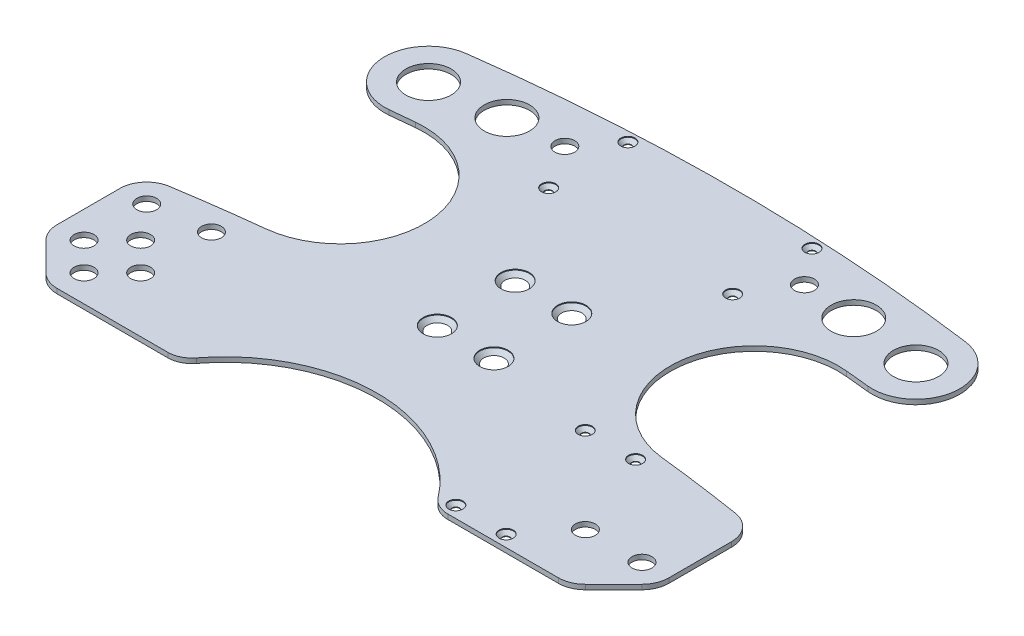
SolidWorks part; units mm, degrees
ref_plane "Front Plane" through (0, 0, 0) normal (0, 0, 1) x (1, 0, 0)
ref_plane "Top Plane" through (0, 0, 0) normal (0, 1, 0) x (1, 0, 0)
ref_plane "Right Plane" through (0, 0, 0) normal (1, 0, 0) x (0, 0, -1)
sketch "Sketch1" plane through (0, 0, 0) normal (0, 1, 0) x (1, 0, 0)
  line L1 (-120, -95) -> (120, -95)
  line L2 (-120, -95) -> (-120, 95)
  line L3 (-120, 95) -> (120, 95)
  line L4 (120, -95) -> (120, 95)
  line L5 (-120, -95) -> (120, 95) construction
  line L6 (-120, 95) -> (120, -95) construction
  line L7 (-10, 13.75) -> (10, 13.75)
  line L8 (-10, 13.75) -> (-10, -13.75)
  line L9 (-10, -13.75) -> (10, -13.75)
  line L10 (10, 13.75) -> (10, -13.75)
  line L11 (-10, 13.75) -> (10, -13.75) construction
  line L12 (-10, -13.75) -> (10, 13.75) construction
  circle A0 centre (0, 0) radius 95
  circle A1 centre (-10, 13.75) radius 2.5
  circle A2 centre (10, 13.75) radius 2.5
  circle A3 centre (10, -13.75) radius 2.5
  circle A4 centre (-10, -13.75) radius 2.5
  circle A5 centre (0, 0) radius 120
  dimension "D3" = 5
  dimension "D1" = 240
  dimension "D2" = 190
  dimension "D4" = 27.5
  dimension "D5" = 20
extrude "Boss-Extrude1" add sketch "Sketch1" along normal blind 1.7 contours A0 A4 L8 A1 L7 A2 L10 A3 L9 | A4 L9 A3 L10 A2 L7 A1 L8 | L3 A5 L1 A0 | L1 A5 L3 A0 region at (-105.6812, 0, 51.9346) region at (68.7642, 0, 68.7642) region at (-92.313, 0, 0) region at (0, 0, 0)
sketch "Sketch2" plane through (0, 1.7, 0) normal (0, 1, 0) x (1, 0, 0)
  line L0 (-81.1673, -40) -> (21.9115, -40) construction
  line L1 (-127.3056, -60) -> (138.909, -60) construction
  line L2 (-88.5406, 28.139) -> (-88.5406, -89.0376) construction
  line L3 (-88.5406, -40) -> (-88.5406, -60) construction
  line L4 (0, 21.6044) -> (0, -21.4213) construction
  line L5 (88.5406, 33.139) -> (88.5406, -84.0376) construction
  line L6 (-151.9803, -25) -> (55.006, -25) construction
  line L7 (-48.8837, 35) -> (62.426, 35) construction
  circle A0 centre (0, 0) radius 35
  circle A1 centre (0, 35) radius 2.5
  circle A2 centre (30.3109, 17.5) radius 2.5
  circle A3 centre (30.3109, -17.5) radius 2.5
  circle A4 centre (0, -35) radius 2.5
  circle A5 centre (-30.3109, -17.5) radius 2.5
  circle A6 centre (-30.3109, 17.5) radius 2.5
  circle A7 centre (-88.5406, -40) radius 3.5
  circle A8 centre (-88.5406, -50) radius 10
  circle A9 centre (-78.5406, -50) radius 3.5
  circle A10 centre (-88.5406, -60) radius 3.5
  circle A11 centre (-98.5406, -50) radius 3.5
  circle A12 centre (78.5406, -50) radius 3.5
  circle A13 centre (98.5406, -50) radius 3.5
  circle A14 centre (-98.5406, -27.8625) radius 3.5
  circle A15 centre (-78.5406, -25) radius 3.5
  circle A16 centre (0, 0) radius 45
  circle A17 centre (0, -580) radius 625
  circle A18 centre (0, -580) radius 645
  circle A19 centre (-86.0945, 59.2282) radius 8
  circle A20 centre (-61.2596, 62.0843) radius 8
  circle A21 centre (-86.0945, 59.2282) radius 15.5
  arc A22 (-73.3144, 95) -> (-73.3144, -95) centre (0, 0) ccw construction
  circle A23 centre (-61.2596, 62.0843) radius 9.5
  circle A24 centre (-86.0945, 59.2282) radius 9.5
  circle A25 centre (61.2596, 62.0843) radius 8
  circle A26 centre (86.0945, 59.2282) radius 8
  circle A27 centre (-42.3209, 63.6101) radius 3.5
  circle A28 centre (0, 0) radius 70
  circle A29 centre (42.3209, 63.6101) radius 3.5
  circle A30 centre (-98.5406, -50) radius 9.5
  circle A31 centre (42.3209, 63.6101) radius 9.5
  circle A32 centre (61.2596, 62.0843) radius 9.5
  circle A33 centre (0, -645.0455) radius 625
  point P17 (0, 0)
  point P21 (-88.5406, -50)
  point P37 (-88.5406, -50)
  point P56 (0, 65)
  point P57 (0, 45)
  point P68 (-76.6704, 60.4269)
  point P69 (-70.7097, 61.1124)
  point P81 (0, 0)
  dimension "D1" = 70
  dimension "D2" = 5
  dimension "D4" = 7
  dimension "D9" = 90
  dimension "D10" = 1250
  dimension "D11" = 20
  dimension "D12" = 16
  dimension "D14" = 6
  dimension "D13" = 19
  dimension "D17" = 140
  dimension "D18" = 6
  dimension "D5" = 20
  dimension "D6" = 40
  dimension "D8" = 15
  dimension "D15" = 6
  dimension "D3" = 6
  dimension "D7" = 4
extrude "Cut-Extrude1" cut sketch "Sketch2" against normal up to next contours A7 | A9 | A10 | A11 | A12 | A13 | A14 | A15 | A19 | A20 | A25 | A26 | A27 | A29
sketch "Sketch3" plane through (0, 1.7, 0) normal (0, 1, 0) x (1, 0, 0)
  line L1 (-84.5506, 43.8053) -> (-40.7771, 48.1872)
  line L2 (0, 100.6986) -> (0, -98.8678) construction
  line L3 (-10.3445, 0) -> (20.4144, 0) construction
  line L5 (84.5506, 43.8053) -> (40.7771, 48.1872)
  line L6 (-42.3209, 63.6101) -> (0, 0) construction
  line L7 (-36.306, 26.5871) -> (-55.2257, 55.0243)
  line L8 (-10.4964, 43.7587) -> (-29.4161, 72.1959)
  line L9 (10.4964, 43.7587) -> (29.4161, 72.1959)
  line L10 (36.306, 26.5871) -> (55.2257, 55.0243)
  line L11 (-108.0406, -50) -> (-108.0406, -27.8625)
  line L13 (-73.3144, -95) -> (73.3144, -95)
  line L14 (73.3144, 95) -> (-73.3144, 95)
  line L15 (-73.3144, -95) -> (73.3144, -95)
  line L16 (73.3144, 95) -> (-73.3144, 95)
  line L17 (-69.0406, -25) -> (-69.0406, -50)
  line L18 (-71.8231, -56.7175) -> (-81.8231, -66.7175)
  line L19 (-105.2581, -56.7175) -> (-95.2581, -66.7175)
  line L20 (-42.3209, 79.1101) -> (42.3209, 79.1101)
  line L21 (-78.5406, -15.5) -> (-42.2463, -15.5)
  line L22 (0, -45) -> (111.243, -45) construction
  line L23 (-88.5406, -69.5) -> (88.5406, -69.5)
  line L24 (69.0406, -15.5) -> (45.0406, -15.5)
  line L25 (78.5406, -15.5) -> (42.2463, -15.5)
  line L27 (108.0406, -50) -> (108.0406, -27.8625)
  line L28 (105.2581, -56.7175) -> (95.2581, -66.7175)
  line L29 (69.0406, -15.5) -> (69.0406, -69.5)
  line L30 (69.0406, -69.5) -> (45.0406, -69.5)
  line L31 (45.0406, -15.5) -> (45.0406, -69.5)
  line L32 (57.0406, -15.5) -> (57.0406, -69.5) construction
  line L33 (45.0406, -42.5) -> (69.0406, -42.5) construction
  circle A0 centre (-86.0945, 59.2282) radius 15.5
  arc A1 (-73.3144, 95) -> (-73.3144, -95) centre (0, 0) ccw construction
  circle A2 centre (-42.3209, 63.6101) radius 15.5
  circle A3 centre (86.0945, 59.2282) radius 15.5
  circle A4 centre (42.3209, 63.6101) radius 15.5
  circle A5 centre (0, 0) radius 45
  circle A6 centre (-98.5406, -27.8625) radius 9.5
  circle A7 centre (-98.5406, -27.8625) radius 3.5 construction
  arc A8 (-73.3144, 95) -> (-73.3144, -95) centre (0, 0) ccw
  arc A9 (73.3144, -95) -> (73.3144, 95) centre (0, 0) ccw
  arc A10 (-73.3144, 95) -> (-73.3144, -95) centre (0, 0) ccw
  arc A11 (73.3144, -95) -> (73.3144, 95) centre (0, 0) ccw
  circle A12 centre (-78.5406, -25) radius 9.5
  circle A13 centre (-88.5406, -60) radius 9.5
  circle A14 centre (-98.5406, -50) radius 9.5
  circle A15 centre (-78.5406, -50) radius 9.5
  circle A17 centre (98.5406, -50) radius 9.5
  circle A18 centre (78.5406, -50) radius 9.5
  arc A19 (73.3144, -95) -> (73.3144, 95) centre (0, 0) ccw construction
  arc A20 (-45.0406, -69.5) -> (45.0406, -69.5) centre (0, -98.6511) cw
  circle A21 centre (98.5406, -27.8625) radius 9.5
  circle A22 centre (98.5406, -50) radius 9.5
  circle A23 centre (88.5406, -60) radius 9.5
  circle A24 centre (-73.1485, 15.1063) radius 29.692
  circle A25 centre (73.1485, 15.1063) radius 29.692
  circle A26 centre (48.1506, -19.64) radius 1.3
  circle A27 centre (65.9306, -19.64) radius 1.3
  circle A28 centre (65.9306, -65.36) radius 1.3
  circle A29 centre (48.1506, -65.36) radius 1.3
  circle A30 centre (0, -580) radius 645
  circle A31 centre (0, -580) radius 660.5
  circle A32 centre (0, -645.0455) radius 634.5
  arc M45 (-73.3144, 95) -> (-73.3144, -95) centre (0, 0) ccw
  line M46 (-73.3144, -95) -> (73.3144, -95)
  arc M47 (73.3144, -95) -> (73.3144, 95) centre (0, 0) ccw
  line M48 (73.3144, 95) -> (-73.3144, 95)
  dimension "D1" = 90
  dimension "D3" = 6
  dimension "D5" = 2.6
  dimension "D4" = 24
  dimension "D6" = 17.78
  dimension "D7" = 45.72
  dimension "D2" = 0
extrude "Cut-Extrude2" cut sketch "Sketch3" against normal up to next contours A24 L1 A0 A14 L11 A6 L21 M45 | A24 | L28 A23 L23 A13 L19 A14 A10 A17 M46 M47 | A20 L23 | L5 A25 L24 L25 A21 L27 A17 A11 A3 | A25 | A30 A0 M45 | A31 A11 M48 M45 | A0 A31 A10 | A31 A3 M47 | A30 A3 M47 | A6 A32 A14 L11 M45 | A11 A32 A21 L27 A17 | A26 | A27 | A28 | A29 region at (-105.8887, 1.7, -12.959) region at (-73.1485, 1.7, -15.1063) region at (-102.839, 1.7, -59.5932) region at (-94.2652, 1.7, -72.7135) region at (0, 1.7, -86.2332) region at (-111.2756, 1.7, 31.2797) region at (0, 1.7, 81.3426) region at (0, 1.7, 59.4787) region at (73.1485, 1.7, -15.1063) region at (105.8887, 1.7, -12.959) region at (111.2756, 1.7, 31.2797) region at (94.2652, 1.7, -72.7135) region at (102.839, 1.7, -59.5932)
hole_wizard "CSK for M5 Flat Head Machine Screw1" positions "Sketch4" profile "Sketch5" countersink size "M5" standard "ANSI Metric"
sketch "Sketch4" plane through (0, 1.7, 0) normal (0, 1, 0) x (1, 0, 0)
  point P0 (-10, 13.75)
  point P3 (10, 13.75)
  point P6 (10, -13.75)
  point P9 (-10, -13.75)
sketch "Sketch5" plane through (-10, 1.7, -13.75) normal (1, 0, 0) x (0, 0, 1)
  line L0 (0, 0) -> (0, 6.5022)
  line L1 (0, 6.5022) -> (2.5, 5)
  line L2 (2.5, 5) -> (2.5, 2.8)
  line L3 (2.5, 2.8) -> (5, 0.3)
  line L4 (5, 0.3) -> (5, 0)
  line L6 (5, 0) -> (0, 0)
  line L7 (-2.5, 2.8) -> (-5, 0.3) construction
  line L10 (0, 6.5022) -> (-2.5, 5) construction
  line L11 (0, -6.35) -> (0, 107.95) construction
  dimension "Hole Dia." = 5
  dimension "Hole Depth" = 5
  dimension "C'Sink Dia." = 10
  dimension "C'Sink Angle" = 90
  dimension "Drill Angle" = 118
  dimension "Head Clearance" = 0.3
sketch "Sketch8" plane through (0, 0, 0) normal (0, -1, 0) x (1, 0, 0)
  line L0 (-69.2596, -62.0843) -> (69.2596, -62.0843) construction
  line L2 (-32.5, -48.0843) -> (32.5, -48.0843)
  line L3 (-32.5, -48.0843) -> (-32.5, -76.0843)
  line L4 (-32.5, -76.0843) -> (32.5, -76.0843)
  line L5 (32.5, -48.0843) -> (32.5, -76.0843)
  line L6 (-32.5, -48.0843) -> (32.5, -76.0843) construction
  line L7 (-32.5, -76.0843) -> (32.5, -48.0843) construction
  circle A0 centre (-61.2596, -62.0843) radius 8 construction
  circle A1 centre (61.2596, -62.0843) radius 8 construction
  circle A2 centre (-32.5, -48.0843) radius 1.3
  circle A3 centre (32.5, -48.0843) radius 1.3
  circle A4 centre (32.5, -76.0843) radius 1.3
  circle A5 centre (-32.5, -76.0843) radius 1.3
  circle A6 centre (48.1506, 19.64) radius 1.3 construction
  point P7 (0, -62.0843)
  dimension "D1" = 65
  dimension "D2" = 28
extrude "Cut-Extrude3" cut sketch "Sketch8" against normal up to next contours A2 | A3 | A4 | A5
hole_wizard "CSK for M2.5 Flat Head Machine Screw1" positions "Sketch6" profile "Sketch7" countersink size "M2.5" standard "ANSI Metric"
sketch "Sketch6" plane through (0, 1.7, 0) normal (0, 1, 0) x (1, 0, 0)
  point P0 (48.1506, -19.64)
  point P3 (65.9306, -19.64)
  point P6 (65.9306, -65.36)
  point P9 (48.1506, -65.36)
  point P27 (32.5, 76.0843)
  point P30 (32.5, 48.0843)
  point P33 (-32.5, 76.0843)
  point P36 (-32.5, 48.0843)
sketch "Sketch7" plane through (48.1506, 1.7, 19.64) normal (1, 0, 0) x (0, 0, 1)
  line L0 (0, 0) -> (0, 5.7511)
  line L1 (0, 5.7511) -> (1.25, 5)
  line L2 (1.25, 5) -> (1.25, 1.55)
  line L3 (1.25, 1.55) -> (2.5, 0.3)
  line L4 (2.5, 0.3) -> (2.5, 0)
  line L6 (2.5, 0) -> (0, 0)
  line L7 (-1.25, 1.55) -> (-2.5, 0.3) construction
  line L10 (0, 5.7511) -> (-1.25, 5) construction
  line L11 (0, -6.35) -> (0, 107.95) construction
  dimension "Hole Dia." = 2.5
  dimension "Hole Depth" = 5
  dimension "C'Sink Dia." = 5
  dimension "C'Sink Angle" = 90
  dimension "Drill Angle" = 118
  dimension "Head Clearance" = 0.3
fillet "Fillet1" radius 8.5 2 edges at (45.0406, 0.85, 69.5) (-45.0406, 0.85, 69.5)
